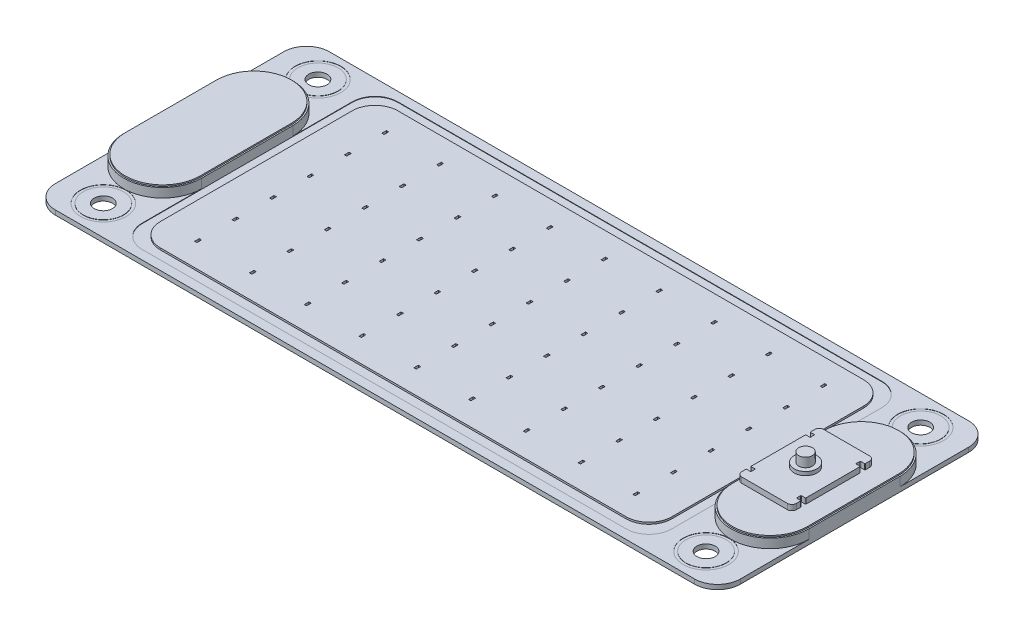
SolidWorks part; units mm, degrees
ref_plane "前视基准面" through (0, 0, 0) normal (0, 0, 1) x (1, 0, 0)
ref_plane "上视基准面" through (0, 0, 0) normal (0, 1, 0) x (1, 0, 0)
ref_plane "右视基准面" through (0, 0, 0) normal (1, 0, 0) x (0, 0, -1)
other "Configuration Table"
ref_plane "基准面1" through (0, 0, 0) normal (0, -1, 0) x (1, 0, 0)
sketch "草图1" plane through (0, 0, 0) normal (0, -1, 0) x (1, 0, 0)
  line L0 (-70, -30) -> (70, -30)
  line L1 (75, -25) -> (75, 25)
  line L2 (70, 30) -> (-70, 30)
  line L3 (-75, 25) -> (-75, -25)
  arc A0 (70, -30) -> (75, -25) centre (70, -25) ccw
  arc A1 (75, 25) -> (70, 30) centre (70, 25) ccw
  arc A2 (-70, 30) -> (-75, 25) centre (-70, 25) ccw
  arc A3 (-75, -25) -> (-70, -30) centre (-70, -25) ccw
extrude "凸台-拉伸1" add sketch "草图1" against normal blind 1
sketch "草图2" plane through (0, 1, 0) normal (0, 1, 0) x (-1, 0, 0)
  line L0 (58, -10) -> (58, 10)
  line L1 (75, 10) -> (75, -10)
  arc A0 (58, 10) -> (75, 10) centre (66.5, 10) cw
  arc A1 (75, -10) -> (58, -10) centre (66.5, -10) cw
extrude "凸台-拉伸2" add sketch "草图2" along normal blind 2
sketch "草图3" plane through (0, 1, 0) normal (0, 1, 0) x (-1, 0, 0)
  line L0 (58, -23) -> (58, 23)
  line L1 (53, 28) -> (-53, 28)
  line L2 (-58, 23) -> (-58, -23)
  line L3 (-53, -28) -> (53, -28)
  arc A0 (58, 23) -> (53, 28) centre (53, 23) ccw
  arc A1 (-53, 28) -> (-58, 23) centre (-53, 23) ccw
  arc A2 (-58, -23) -> (-53, -28) centre (-53, -23) ccw
  arc A3 (53, -28) -> (58, -23) centre (53, -23) ccw
extrude "切除-拉伸1" cut sketch "草图3" against normal blind 0.1
sketch "草图4" plane through (0, 1, 0) normal (0, 1, 0) x (-1, 0, 0)
  line L0 (-75, -10) -> (-75, 10)
  line L1 (-58, 10) -> (-58, -10)
  arc A0 (-58, -10) -> (-75, -10) centre (-66.5, -10) cw
  arc A1 (-75, 10) -> (-58, 10) centre (-66.5, 10) cw
extrude "凸台-拉伸3" add sketch "草图4" along normal blind 2
sketch "草图5" plane through (0, 3, 0) normal (0, 1, 0) x (-1, 0, 0)
  line L0 (-74.7, -10) -> (-74.7, 10)
  line L1 (-58.3, 10) -> (-58.3, -10)
  arc A0 (-74.7, 10) -> (-58.3, 10) centre (-66.5, 10) cw
  arc A1 (-58.3, -10) -> (-74.7, -10) centre (-66.5, -10) cw
extrude "凸台-拉伸4" add sketch "草图5" along normal blind 0.3
sketch "草图6" plane through (0, 3.3, 0) normal (0, 1, 0) x (-1, 0, 0)
  line L0 (-59.3, -9) -> (-69.3, -9)
  line L1 (-70.3, -8) -> (-70.3, -7.1)
  line L2 (-70.2, -7) -> (-69.4, -7)
  line L3 (-69.3, -6.9) -> (-69.3, -6.1)
  line L4 (-69.4, -6) -> (-70.2, -6)
  line L5 (-70.3, -5.9) -> (-70.3, 5.9)
  line L6 (-70.2, 6) -> (-69.4, 6)
  line L7 (-69.3, 6.1) -> (-69.3, 6.9)
  line L8 (-69.4, 7) -> (-70.2, 7)
  line L9 (-70.3, 7.1) -> (-70.3, 8)
  line L10 (-69.3, 9) -> (-59.3, 9)
  line L11 (-58.3, 8) -> (-58.3, -8)
  line L12 (-58.3, -10) -> (-58.3, 10) construction
  arc A0 (-58.3, -8) -> (-59.3, -9) centre (-59.3, -8) cw
  arc A1 (-69.3, -9) -> (-70.3, -8) centre (-69.3, -8) cw
  arc A2 (-70.3, -7.1) -> (-70.2, -7) centre (-70.2, -7.1) cw
  arc A3 (-69.4, -7) -> (-69.3, -6.9) centre (-69.4, -6.9) ccw
  arc A4 (-69.3, -6.1) -> (-69.4, -6) centre (-69.4, -6.1) ccw
  arc A5 (-70.2, -6) -> (-70.3, -5.9) centre (-70.2, -5.9) cw
  arc A6 (-70.3, 5.9) -> (-70.2, 6) centre (-70.2, 5.9) cw
  arc A7 (-69.4, 6) -> (-69.3, 6.1) centre (-69.4, 6.1) ccw
  arc A8 (-69.3, 6.9) -> (-69.4, 7) centre (-69.4, 6.9) ccw
  arc A9 (-70.2, 7) -> (-70.3, 7.1) centre (-70.2, 7.1) cw
  arc A10 (-70.3, 8) -> (-69.3, 9) centre (-69.3, 8) cw
  arc A11 (-59.3, 9) -> (-58.3, 8) centre (-59.3, 8) cw
extrude "凸台-拉伸5" add sketch "草图6" along normal blind 1.2
sketch "草图7" plane through (0, 4.5, 0) normal (0, 1, 0) x (-1, 0, 0)
  line L0 (-58.4, 7) -> (-59.2, 7)
  line L1 (-59.3, 6.9) -> (-59.3, 6.1)
  line L2 (-59.2, 6) -> (-58.4, 6)
  line L3 (-58.3, 5.9) -> (-58.3, 7.1)
  arc A0 (-58.3, 7.1) -> (-58.4, 7) centre (-58.4, 7.1) cw
  arc A1 (-59.2, 7) -> (-59.3, 6.9) centre (-59.2, 6.9) ccw
  arc A2 (-59.3, 6.1) -> (-59.2, 6) centre (-59.2, 6.1) ccw
  arc A3 (-58.4, 6) -> (-58.3, 5.9) centre (-58.4, 5.9) cw
extrude "切除-拉伸2" cut sketch "草图7" against normal blind 1.2
sketch "草图8" plane through (0, 4.5, 0) normal (0, 1, 0) x (-1, 0, 0)
  line L0 (-58.4, -6) -> (-59.2, -6)
  line L1 (-59.3, -6.1) -> (-59.3, -6.9)
  line L2 (-59.2, -7) -> (-58.4, -7)
  line L3 (-58.3, -7.1) -> (-58.3, -5.9)
  arc A0 (-58.3, -5.9) -> (-58.4, -6) centre (-58.4, -5.9) cw
  arc A1 (-59.2, -6) -> (-59.3, -6.1) centre (-59.2, -6.1) ccw
  arc A2 (-59.3, -6.9) -> (-59.2, -7) centre (-59.2, -6.9) ccw
  arc A3 (-58.4, -7) -> (-58.3, -7.1) centre (-58.4, -7.1) cw
extrude "切除-拉伸3" cut sketch "草图8" against normal blind 1.2
sketch "草图9" plane through (0, 3, 0) normal (0, 1, 0) x (-1, 0, 0)
  line L0 (74.7, 10) -> (74.7, -10)
  line L1 (58.3, -10) -> (58.3, 10)
  arc A0 (58.3, 10) -> (74.7, 10) centre (66.5, 10) cw
  arc A1 (74.7, -10) -> (58.3, -10) centre (66.5, -10) cw
extrude "凸台-拉伸6" add sketch "草图9" along normal blind 0.3
sketch "草图10" plane through (0, 0.9, 0) normal (0, 1, 0) x (-1, 0, 0)
  line L0 (51, -26) -> (-51, -26)
  line L1 (-56, -21) -> (-56, 21)
  line L2 (-51, 26) -> (51, 26)
  line L3 (56, 21) -> (56, -21)
  arc A0 (56, -21) -> (51, -26) centre (51, -21) cw
  arc A1 (-51, -26) -> (-56, -21) centre (-51, -21) cw
  arc A2 (-56, 21) -> (-51, 26) centre (-51, 21) cw
  arc A3 (51, 26) -> (56, 21) centre (51, 21) cw
extrude "凸台-拉伸7" add sketch "草图10" along normal blind 0.4
sketch "草图11" plane through (0, 1.3, 0) normal (0, 1, 0) x (-1, 0, 0)
  line L0 (48.5, -21) -> (48.5, -20)
  line L1 (48.5, -20) -> (48, -20)
  line L2 (48, -20) -> (48, -21)
  line L3 (48, -21) -> (48.5, -21)
extrude "切除-拉伸4" cut sketch "草图11" against normal blind 0.5
sketch "草图12" plane through (0, 1.3, 0) normal (0, 1, 0) x (-1, 0, 0)
  line L0 (36.5, -21) -> (36.5, -20)
  line L1 (36.5, -20) -> (36, -20)
  line L2 (36, -20) -> (36, -21)
  line L3 (36, -21) -> (36.5, -21)
extrude "切除-拉伸5" cut sketch "草图12" against normal blind 0.5
sketch "草图13" plane through (0, 1.3, 0) normal (0, 1, 0) x (-1, 0, 0)
  line L0 (24.5, -21) -> (24.5, -20)
  line L1 (24.5, -20) -> (24, -20)
  line L2 (24, -20) -> (24, -21)
  line L3 (24, -21) -> (24.5, -21)
extrude "切除-拉伸6" cut sketch "草图13" against normal blind 0.5
sketch "草图14" plane through (0, 1.3, 0) normal (0, 1, 0) x (-1, 0, 0)
  line L0 (12.5, -21) -> (12.5, -20)
  line L1 (12.5, -20) -> (12, -20)
  line L2 (12, -20) -> (12, -21)
  line L3 (12, -21) -> (12.5, -21)
extrude "切除-拉伸7" cut sketch "草图14" against normal blind 0.5
sketch "草图15" plane through (0, 1.3, 0) normal (0, 1, 0) x (-1, 0, 0)
  line L0 (0.5, -21) -> (0.5, -20)
  line L1 (0.5, -20) -> (0, -20)
  line L2 (0, -20) -> (0, -21)
  line L3 (0, -21) -> (0.5, -21)
extrude "切除-拉伸8" cut sketch "草图15" against normal blind 0.5
sketch "草图16" plane through (0, 1.3, 0) normal (0, 1, 0) x (-1, 0, 0)
  line L0 (-11.5, -21) -> (-11.5, -20)
  line L1 (-11.5, -20) -> (-12, -20)
  line L2 (-12, -20) -> (-12, -21)
  line L3 (-12, -21) -> (-11.5, -21)
extrude "切除-拉伸9" cut sketch "草图16" against normal blind 0.5
sketch "草图17" plane through (0, 1.3, 0) normal (0, 1, 0) x (-1, 0, 0)
  line L0 (-23.5, -21) -> (-23.5, -20)
  line L1 (-23.5, -20) -> (-24, -20)
  line L2 (-24, -20) -> (-24, -21)
  line L3 (-24, -21) -> (-23.5, -21)
extrude "切除-拉伸10" cut sketch "草图17" against normal blind 0.5
sketch "草图18" plane through (0, 1.3, 0) normal (0, 1, 0) x (-1, 0, 0)
  line L0 (-35.5, -21) -> (-35.5, -20)
  line L1 (-35.5, -20) -> (-36, -20)
  line L2 (-36, -20) -> (-36, -21)
  line L3 (-36, -21) -> (-35.5, -21)
extrude "切除-拉伸11" cut sketch "草图18" against normal blind 0.5
sketch "草图19" plane through (0, 1.3, 0) normal (0, 1, 0) x (-1, 0, 0)
  line L0 (-47.5, -21) -> (-47.5, -20)
  line L1 (-47.5, -20) -> (-48, -20)
  line L2 (-48, -20) -> (-48, -21)
  line L3 (-48, -21) -> (-47.5, -21)
extrude "切除-拉伸12" cut sketch "草图19" against normal blind 0.5
sketch "草图20" plane through (0, 1.3, 0) normal (0, 1, 0) x (-1, 0, 0)
  line L0 (48.5, -12.8) -> (48.5, -11.8)
  line L1 (48.5, -11.8) -> (48, -11.8)
  line L2 (48, -11.8) -> (48, -12.8)
  line L3 (48, -12.8) -> (48.5, -12.8)
extrude "切除-拉伸13" cut sketch "草图20" against normal blind 0.5
sketch "草图21" plane through (0, 1.3, 0) normal (0, 1, 0) x (-1, 0, 0)
  line L0 (36.5, -12.8) -> (36.5, -11.8)
  line L1 (36.5, -11.8) -> (36, -11.8)
  line L2 (36, -11.8) -> (36, -12.8)
  line L3 (36, -12.8) -> (36.5, -12.8)
extrude "切除-拉伸14" cut sketch "草图21" against normal blind 0.5
sketch "草图22" plane through (0, 1.3, 0) normal (0, 1, 0) x (-1, 0, 0)
  line L0 (24.5, -12.8) -> (24.5, -11.8)
  line L1 (24.5, -11.8) -> (24, -11.8)
  line L2 (24, -11.8) -> (24, -12.8)
  line L3 (24, -12.8) -> (24.5, -12.8)
extrude "切除-拉伸15" cut sketch "草图22" against normal blind 0.5
sketch "草图23" plane through (0, 1.3, 0) normal (0, 1, 0) x (-1, 0, 0)
  line L0 (12.5, -12.8) -> (12.5, -11.8)
  line L1 (12.5, -11.8) -> (12, -11.8)
  line L2 (12, -11.8) -> (12, -12.8)
  line L3 (12, -12.8) -> (12.5, -12.8)
extrude "切除-拉伸16" cut sketch "草图23" against normal blind 0.5
sketch "草图24" plane through (0, 1.3, 0) normal (0, 1, 0) x (-1, 0, 0)
  line L0 (0.5, -12.8) -> (0.5, -11.8)
  line L1 (0.5, -11.8) -> (0, -11.8)
  line L2 (0, -11.8) -> (0, -12.8)
  line L3 (0, -12.8) -> (0.5, -12.8)
extrude "切除-拉伸17" cut sketch "草图24" against normal blind 0.5
sketch "草图25" plane through (0, 1.3, 0) normal (0, 1, 0) x (-1, 0, 0)
  line L0 (-11.5, -12.8) -> (-11.5, -11.8)
  line L1 (-11.5, -11.8) -> (-12, -11.8)
  line L2 (-12, -11.8) -> (-12, -12.8)
  line L3 (-12, -12.8) -> (-11.5, -12.8)
extrude "切除-拉伸18" cut sketch "草图25" against normal blind 0.5
sketch "草图26" plane through (0, 1.3, 0) normal (0, 1, 0) x (-1, 0, 0)
  line L0 (-23.5, -12.8) -> (-23.5, -11.8)
  line L1 (-23.5, -11.8) -> (-24, -11.8)
  line L2 (-24, -11.8) -> (-24, -12.8)
  line L3 (-24, -12.8) -> (-23.5, -12.8)
extrude "切除-拉伸19" cut sketch "草图26" against normal blind 0.5
sketch "草图27" plane through (0, 1.3, 0) normal (0, 1, 0) x (-1, 0, 0)
  line L0 (-35.5, -12.8) -> (-35.5, -11.8)
  line L1 (-35.5, -11.8) -> (-36, -11.8)
  line L2 (-36, -11.8) -> (-36, -12.8)
  line L3 (-36, -12.8) -> (-35.5, -12.8)
extrude "切除-拉伸20" cut sketch "草图27" against normal blind 0.5
sketch "草图28" plane through (0, 1.3, 0) normal (0, 1, 0) x (-1, 0, 0)
  line L0 (-47.5, -12.8) -> (-47.5, -11.8)
  line L1 (-47.5, -11.8) -> (-48, -11.8)
  line L2 (-48, -11.8) -> (-48, -12.8)
  line L3 (-48, -12.8) -> (-47.5, -12.8)
extrude "切除-拉伸21" cut sketch "草图28" against normal blind 0.5
sketch "草图29" plane through (0, 1.3, 0) normal (0, 1, 0) x (-1, 0, 0)
  line L0 (48.5, -4.6) -> (48.5, -3.6)
  line L1 (48.5, -3.6) -> (48, -3.6)
  line L2 (48, -3.6) -> (48, -4.6)
  line L3 (48, -4.6) -> (48.5, -4.6)
extrude "切除-拉伸22" cut sketch "草图29" against normal blind 0.5
sketch "草图30" plane through (0, 1.3, 0) normal (0, 1, 0) x (-1, 0, 0)
  line L0 (36.5, -4.6) -> (36.5, -3.6)
  line L1 (36.5, -3.6) -> (36, -3.6)
  line L2 (36, -3.6) -> (36, -4.6)
  line L3 (36, -4.6) -> (36.5, -4.6)
extrude "切除-拉伸23" cut sketch "草图30" against normal blind 0.5
sketch "草图31" plane through (0, 1.3, 0) normal (0, 1, 0) x (-1, 0, 0)
  line L0 (24.5, -4.6) -> (24.5, -3.6)
  line L1 (24.5, -3.6) -> (24, -3.6)
  line L2 (24, -3.6) -> (24, -4.6)
  line L3 (24, -4.6) -> (24.5, -4.6)
extrude "切除-拉伸24" cut sketch "草图31" against normal blind 0.5
sketch "草图32" plane through (0, 1.3, 0) normal (0, 1, 0) x (-1, 0, 0)
  line L0 (12.5, -4.6) -> (12.5, -3.6)
  line L1 (12.5, -3.6) -> (12, -3.6)
  line L2 (12, -3.6) -> (12, -4.6)
  line L3 (12, -4.6) -> (12.5, -4.6)
extrude "切除-拉伸25" cut sketch "草图32" against normal blind 0.5
sketch "草图33" plane through (0, 1.3, 0) normal (0, 1, 0) x (-1, 0, 0)
  line L0 (0.5, -4.6) -> (0.5, -3.6)
  line L1 (0.5, -3.6) -> (0, -3.6)
  line L2 (0, -3.6) -> (0, -4.6)
  line L3 (0, -4.6) -> (0.5, -4.6)
extrude "切除-拉伸26" cut sketch "草图33" against normal blind 0.5
sketch "草图34" plane through (0, 1.3, 0) normal (0, 1, 0) x (-1, 0, 0)
  line L0 (-11.5, -4.6) -> (-11.5, -3.6)
  line L1 (-11.5, -3.6) -> (-12, -3.6)
  line L2 (-12, -3.6) -> (-12, -4.6)
  line L3 (-12, -4.6) -> (-11.5, -4.6)
extrude "切除-拉伸27" cut sketch "草图34" against normal blind 0.5
sketch "草图35" plane through (0, 1.3, 0) normal (0, 1, 0) x (-1, 0, 0)
  line L0 (-23.5, -4.6) -> (-23.5, -3.6)
  line L1 (-23.5, -3.6) -> (-24, -3.6)
  line L2 (-24, -3.6) -> (-24, -4.6)
  line L3 (-24, -4.6) -> (-23.5, -4.6)
extrude "切除-拉伸28" cut sketch "草图35" against normal blind 0.5
sketch "草图36" plane through (0, 1.3, 0) normal (0, 1, 0) x (-1, 0, 0)
  line L0 (-35.5, -4.6) -> (-35.5, -3.6)
  line L1 (-35.5, -3.6) -> (-36, -3.6)
  line L2 (-36, -3.6) -> (-36, -4.6)
  line L3 (-36, -4.6) -> (-35.5, -4.6)
extrude "切除-拉伸29" cut sketch "草图36" against normal blind 0.5
sketch "草图37" plane through (0, 1.3, 0) normal (0, 1, 0) x (-1, 0, 0)
  line L0 (-47.5, -4.6) -> (-47.5, -3.6)
  line L1 (-47.5, -3.6) -> (-48, -3.6)
  line L2 (-48, -3.6) -> (-48, -4.6)
  line L3 (-48, -4.6) -> (-47.5, -4.6)
extrude "切除-拉伸30" cut sketch "草图37" against normal blind 0.5
sketch "草图38" plane through (0, 1.3, 0) normal (0, 1, 0) x (-1, 0, 0)
  line L0 (48.5, 3.6) -> (48.5, 4.6)
  line L1 (48.5, 4.6) -> (48, 4.6)
  line L2 (48, 4.6) -> (48, 3.6)
  line L3 (48, 3.6) -> (48.5, 3.6)
extrude "切除-拉伸31" cut sketch "草图38" against normal blind 0.5
sketch "草图39" plane through (0, 1.3, 0) normal (0, 1, 0) x (-1, 0, 0)
  line L0 (36.5, 3.6) -> (36.5, 4.6)
  line L1 (36.5, 4.6) -> (36, 4.6)
  line L2 (36, 4.6) -> (36, 3.6)
  line L3 (36, 3.6) -> (36.5, 3.6)
extrude "切除-拉伸32" cut sketch "草图39" against normal blind 0.5
sketch "草图40" plane through (0, 1.3, 0) normal (0, 1, 0) x (-1, 0, 0)
  line L0 (24.5, 3.6) -> (24.5, 4.6)
  line L1 (24.5, 4.6) -> (24, 4.6)
  line L2 (24, 4.6) -> (24, 3.6)
  line L3 (24, 3.6) -> (24.5, 3.6)
extrude "切除-拉伸33" cut sketch "草图40" against normal blind 0.5
sketch "草图41" plane through (0, 1.3, 0) normal (0, 1, 0) x (-1, 0, 0)
  line L0 (12.5, 3.6) -> (12.5, 4.6)
  line L1 (12.5, 4.6) -> (12, 4.6)
  line L2 (12, 4.6) -> (12, 3.6)
  line L3 (12, 3.6) -> (12.5, 3.6)
extrude "切除-拉伸34" cut sketch "草图41" against normal blind 0.5
sketch "草图42" plane through (0, 1.3, 0) normal (0, 1, 0) x (-1, 0, 0)
  line L0 (0.5, 3.6) -> (0.5, 4.6)
  line L1 (0.5, 4.6) -> (0, 4.6)
  line L2 (0, 4.6) -> (0, 3.6)
  line L3 (0, 3.6) -> (0.5, 3.6)
extrude "切除-拉伸35" cut sketch "草图42" against normal blind 0.5
sketch "草图43" plane through (0, 1.3, 0) normal (0, 1, 0) x (-1, 0, 0)
  line L0 (-11.5, 3.6) -> (-11.5, 4.6)
  line L1 (-11.5, 4.6) -> (-12, 4.6)
  line L2 (-12, 4.6) -> (-12, 3.6)
  line L3 (-12, 3.6) -> (-11.5, 3.6)
extrude "切除-拉伸36" cut sketch "草图43" against normal blind 0.5
sketch "草图44" plane through (0, 1.3, 0) normal (0, 1, 0) x (-1, 0, 0)
  line L0 (-23.5, 3.6) -> (-23.5, 4.6)
  line L1 (-23.5, 4.6) -> (-24, 4.6)
  line L2 (-24, 4.6) -> (-24, 3.6)
  line L3 (-24, 3.6) -> (-23.5, 3.6)
extrude "切除-拉伸37" cut sketch "草图44" against normal blind 0.5
sketch "草图45" plane through (0, 1.3, 0) normal (0, 1, 0) x (-1, 0, 0)
  line L0 (-35.5, 3.6) -> (-35.5, 4.6)
  line L1 (-35.5, 4.6) -> (-36, 4.6)
  line L2 (-36, 4.6) -> (-36, 3.6)
  line L3 (-36, 3.6) -> (-35.5, 3.6)
extrude "切除-拉伸38" cut sketch "草图45" against normal blind 0.5
sketch "草图46" plane through (0, 1.3, 0) normal (0, 1, 0) x (-1, 0, 0)
  line L0 (-47.5, 3.6) -> (-47.5, 4.6)
  line L1 (-47.5, 4.6) -> (-48, 4.6)
  line L2 (-48, 4.6) -> (-48, 3.6)
  line L3 (-48, 3.6) -> (-47.5, 3.6)
extrude "切除-拉伸39" cut sketch "草图46" against normal blind 0.5
sketch "草图47" plane through (0, 1.3, 0) normal (0, 1, 0) x (-1, 0, 0)
  line L0 (48.5, 11.8) -> (48.5, 12.8)
  line L1 (48.5, 12.8) -> (48, 12.8)
  line L2 (48, 12.8) -> (48, 11.8)
  line L3 (48, 11.8) -> (48.5, 11.8)
extrude "切除-拉伸40" cut sketch "草图47" against normal blind 0.5
sketch "草图48" plane through (0, 1.3, 0) normal (0, 1, 0) x (-1, 0, 0)
  line L0 (36.5, 11.8) -> (36.5, 12.8)
  line L1 (36.5, 12.8) -> (36, 12.8)
  line L2 (36, 12.8) -> (36, 11.8)
  line L3 (36, 11.8) -> (36.5, 11.8)
extrude "切除-拉伸41" cut sketch "草图48" against normal blind 0.5
sketch "草图49" plane through (0, 1.3, 0) normal (0, 1, 0) x (-1, 0, 0)
  line L0 (24.5, 11.8) -> (24.5, 12.8)
  line L1 (24.5, 12.8) -> (24, 12.8)
  line L2 (24, 12.8) -> (24, 11.8)
  line L3 (24, 11.8) -> (24.5, 11.8)
extrude "切除-拉伸42" cut sketch "草图49" against normal blind 0.5
sketch "草图50" plane through (0, 1.3, 0) normal (0, 1, 0) x (-1, 0, 0)
  line L0 (12.5, 11.8) -> (12.5, 12.8)
  line L1 (12.5, 12.8) -> (12, 12.8)
  line L2 (12, 12.8) -> (12, 11.8)
  line L3 (12, 11.8) -> (12.5, 11.8)
extrude "切除-拉伸43" cut sketch "草图50" against normal blind 0.5
sketch "草图51" plane through (0, 1.3, 0) normal (0, 1, 0) x (-1, 0, 0)
  line L0 (0.5, 11.8) -> (0.5, 12.8)
  line L1 (0.5, 12.8) -> (0, 12.8)
  line L2 (0, 12.8) -> (0, 11.8)
  line L3 (0, 11.8) -> (0.5, 11.8)
extrude "切除-拉伸44" cut sketch "草图51" against normal blind 0.5
sketch "草图52" plane through (0, 1.3, 0) normal (0, 1, 0) x (-1, 0, 0)
  line L0 (-11.5, 11.8) -> (-11.5, 12.8)
  line L1 (-11.5, 12.8) -> (-12, 12.8)
  line L2 (-12, 12.8) -> (-12, 11.8)
  line L3 (-12, 11.8) -> (-11.5, 11.8)
extrude "切除-拉伸45" cut sketch "草图52" against normal blind 0.5
sketch "草图53" plane through (0, 1.3, 0) normal (0, 1, 0) x (-1, 0, 0)
  line L0 (-23.5, 11.8) -> (-23.5, 12.8)
  line L1 (-23.5, 12.8) -> (-24, 12.8)
  line L2 (-24, 12.8) -> (-24, 11.8)
  line L3 (-24, 11.8) -> (-23.5, 11.8)
extrude "切除-拉伸46" cut sketch "草图53" against normal blind 0.5
sketch "草图54" plane through (0, 1.3, 0) normal (0, 1, 0) x (-1, 0, 0)
  line L0 (-35.5, 11.8) -> (-35.5, 12.8)
  line L1 (-35.5, 12.8) -> (-36, 12.8)
  line L2 (-36, 12.8) -> (-36, 11.8)
  line L3 (-36, 11.8) -> (-35.5, 11.8)
extrude "切除-拉伸47" cut sketch "草图54" against normal blind 0.5
sketch "草图55" plane through (0, 1.3, 0) normal (0, 1, 0) x (-1, 0, 0)
  line L0 (-47.5, 11.8) -> (-47.5, 12.8)
  line L1 (-47.5, 12.8) -> (-48, 12.8)
  line L2 (-48, 12.8) -> (-48, 11.8)
  line L3 (-48, 11.8) -> (-47.5, 11.8)
extrude "切除-拉伸48" cut sketch "草图55" against normal blind 0.5
sketch "草图56" plane through (0, 1.3, 0) normal (0, 1, 0) x (-1, 0, 0)
  line L0 (48.5, 20) -> (48.5, 21)
  line L1 (48.5, 21) -> (48, 21)
  line L2 (48, 21) -> (48, 20)
  line L3 (48, 20) -> (48.5, 20)
extrude "切除-拉伸49" cut sketch "草图56" against normal blind 0.5
sketch "草图57" plane through (0, 1.3, 0) normal (0, 1, 0) x (-1, 0, 0)
  line L0 (36.5, 20) -> (36.5, 21)
  line L1 (36.5, 21) -> (36, 21)
  line L2 (36, 21) -> (36, 20)
  line L3 (36, 20) -> (36.5, 20)
extrude "切除-拉伸50" cut sketch "草图57" against normal blind 0.5
sketch "草图58" plane through (0, 1.3, 0) normal (0, 1, 0) x (-1, 0, 0)
  line L0 (24.5, 20) -> (24.5, 21)
  line L1 (24.5, 21) -> (24, 21)
  line L2 (24, 21) -> (24, 20)
  line L3 (24, 20) -> (24.5, 20)
extrude "切除-拉伸51" cut sketch "草图58" against normal blind 0.5
sketch "草图59" plane through (0, 1.3, 0) normal (0, 1, 0) x (-1, 0, 0)
  line L0 (12.5, 20) -> (12.5, 21)
  line L1 (12.5, 21) -> (12, 21)
  line L2 (12, 21) -> (12, 20)
  line L3 (12, 20) -> (12.5, 20)
extrude "切除-拉伸52" cut sketch "草图59" against normal blind 0.5
sketch "草图60" plane through (0, 1.3, 0) normal (0, 1, 0) x (-1, 0, 0)
  line L0 (0.5, 20) -> (0.5, 21)
  line L1 (0.5, 21) -> (0, 21)
  line L2 (0, 21) -> (0, 20)
  line L3 (0, 20) -> (0.5, 20)
extrude "切除-拉伸53" cut sketch "草图60" against normal blind 0.5
sketch "草图61" plane through (0, 1.3, 0) normal (0, 1, 0) x (-1, 0, 0)
  line L0 (-11.5, 20) -> (-11.5, 21)
  line L1 (-11.5, 21) -> (-12, 21)
  line L2 (-12, 21) -> (-12, 20)
  line L3 (-12, 20) -> (-11.5, 20)
extrude "切除-拉伸54" cut sketch "草图61" against normal blind 0.5
sketch "草图62" plane through (0, 1.3, 0) normal (0, 1, 0) x (-1, 0, 0)
  line L0 (-23.5, 20) -> (-23.5, 21)
  line L1 (-23.5, 21) -> (-24, 21)
  line L2 (-24, 21) -> (-24, 20)
  line L3 (-24, 20) -> (-23.5, 20)
extrude "切除-拉伸55" cut sketch "草图62" against normal blind 0.5
sketch "草图63" plane through (0, 1.3, 0) normal (0, 1, 0) x (-1, 0, 0)
  line L0 (-35.5, 20) -> (-35.5, 21)
  line L1 (-35.5, 21) -> (-36, 21)
  line L2 (-36, 21) -> (-36, 20)
  line L3 (-36, 20) -> (-35.5, 20)
extrude "切除-拉伸56" cut sketch "草图63" against normal blind 0.5
sketch "草图64" plane through (0, 1.3, 0) normal (0, 1, 0) x (-1, 0, 0)
  line L0 (-47.5, 20) -> (-47.5, 21)
  line L1 (-47.5, 21) -> (-48, 21)
  line L2 (-48, 21) -> (-48, 20)
  line L3 (-48, 20) -> (-47.5, 20)
extrude "切除-拉伸57" cut sketch "草图64" against normal blind 0.5
sketch "草图65" plane through (0, 1, 0) normal (0, 1, 0) x (-1, 0, 0)
  circle A0 centre (66, -23.4981) radius 5.0073
extrude "切除-拉伸58" cut sketch "草图65" against normal blind 0.05
sketch "草图66" plane through (0, 1, 0) normal (0, 1, 0) x (-1, 0, 0)
  circle A0 centre (-66, -23.4981) radius 5.0073
extrude "切除-拉伸59" cut sketch "草图66" against normal blind 0.05
sketch "草图67" plane through (0, 1, 0) normal (0, 1, 0) x (-1, 0, 0)
  circle A0 centre (-66, 23.4981) radius 5.0073
extrude "切除-拉伸60" cut sketch "草图67" against normal blind 0.05
sketch "草图68" plane through (0, 1, 0) normal (0, 1, 0) x (-1, 0, 0)
  circle A0 centre (66, 23.4981) radius 5.0073
extrude "切除-拉伸61" cut sketch "草图68" against normal blind 0.05
ref_plane "基准面2" through (0, 0, -23.4981) normal (0, 0, -1) x (-1, 0, 0)
sketch "草图69" plane through (0, 0, -23.4981) normal (0, 0, -1) x (-1, 0, 0)
  line L0 (61.6, 0.95) -> (66, 0.95)
  line L1 (66, 0.95) -> (66, 1)
  line L2 (66, 1) -> (61.6, 1)
  line L3 (61.6, 1) -> (61.6, 0.95)
  line L4 (66, 0.95) -> (66, 1) construction
revolve "旋转1" add sketch "草图69" angle 360 about L4 reverse direction yes
sketch "草图70" plane through (0, 0, -23.4981) normal (0, 0, -1) x (-1, 0, 0)
  line L0 (-70.4, 0.95) -> (-66, 0.95)
  line L1 (-66, 0.95) -> (-66, 1)
  line L2 (-66, 1) -> (-70.4, 1)
  line L3 (-70.4, 1) -> (-70.4, 0.95)
  line L4 (-66, 0.95) -> (-66, 1) construction
revolve "旋转2" add sketch "草图70" angle 360 about L4 reverse direction yes
ref_plane "基准面3" through (0, 0, 23.4981) normal (0, 0, -1) x (-1, 0, 0)
sketch "草图71" plane through (0, 0, 23.4981) normal (0, 0, -1) x (-1, 0, 0)
  line L0 (-70.4, 0.95) -> (-66, 0.95)
  line L1 (-66, 0.95) -> (-66, 1)
  line L2 (-66, 1) -> (-70.4, 1)
  line L3 (-70.4, 1) -> (-70.4, 0.95)
  line L4 (-66, 0.95) -> (-66, 1) construction
revolve "旋转3" add sketch "草图71" angle 360 about L4 reverse direction yes
sketch "草图72" plane through (0, 0, 23.4981) normal (0, 0, -1) x (-1, 0, 0)
  line L0 (61.6, 0.95) -> (66, 0.95)
  line L1 (66, 0.95) -> (66, 1)
  line L2 (66, 1) -> (61.6, 1)
  line L3 (61.6, 1) -> (61.6, 0.95)
  line L4 (66, 0.95) -> (66, 1) construction
revolve "旋转4" add sketch "草图72" angle 360 about L4 reverse direction yes
ref_plane "基准面4" through (0, 0, 0) normal (0, 0, -1) x (-1, 0, 0)
sketch "草图73" plane through (0, 0, 0) normal (0, 0, -1) x (-1, 0, 0)
  line L0 (-66.8, 4.5) -> (-64.3, 4.5)
  line L1 (-64.3, 4.5) -> (-64.3, 7.3)
  line L2 (-64.3, 7.3) -> (-65.8, 7.3)
  line L3 (-65.8, 7.3) -> (-65.8, 5.3)
  line L4 (-65.8, 5.3) -> (-66.8, 5.3)
  line L5 (-66.8, 5.3) -> (-66.8, 4.5)
  line L6 (-64.3, 4.5) -> (-64.3, 7.3) construction
revolve "旋转5" add sketch "草图73" angle 360 about L6 reverse direction yes
hole_wizard "Ø4.0 (4) 直径孔1" positions "草图75" profile "草图74" hole size "Ø4.0" standard "ANSI Metric"
sketch "草图75" plane through (0, 0, 0) normal (0, -1, 0) x (-1, 0, 0)
  point P0 (-66, 23.4981)
  point P1 (-66, -23.4981)
  point P2 (66, -23.4981)
  point P3 (66, 23.4981)
sketch "草图74" plane through (66, 0, -23.4981) normal (1, 0, 0) x (0, 0, -1)
  line L0 (0, 0) -> (0, 7.3)
  line L1 (0, 7.3) -> (2, 7.3)
  line L2 (2, 7.3) -> (2, 0)
  line L5 (2, 0) -> (0, 0)
  line L11 (0, -6.35) -> (0, 107.95) construction
  dimension "通孔孔直径" = 4
  dimension "通孔孔深度" = 7.3
hole_wizard "Ø2.0 (2) 直径孔1" positions "草图77" profile "草图76" hole size "Ø2.0" standard "ANSI Metric"
sketch "草图77" plane through (0, 0, 0) normal (0, -1, 0) x (-1, 0, 0)
  point P0 (70.7, -2)
  point P1 (70.7, 2)
sketch "草图76" plane through (-70.7, 0, 2) normal (1, 0, 0) x (0, 0, -1)
  line L0 (0, 0) -> (0, 2)
  line L1 (0, 2) -> (1, 2)
  line L2 (1, 2) -> (1, 0)
  line L5 (1, 0) -> (0, 0)
  line L10 (0, 2) -> (-1, 2) construction
  line L11 (0, -6.35) -> (0, 107.95) construction
  dimension "孔直径" = 2
  dimension "孔深度" = 2
  dimension "导头角度" = 180
